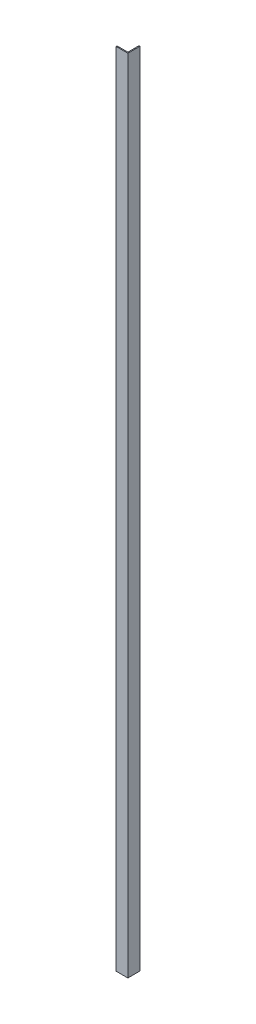
SolidWorks part; units mm, degrees
material "AISI 1035 Steel (SS)"
ref_plane "Front Plane" through (0, 0, 0) normal (0, 0, 1) x (1, 0, 0)
ref_plane "Top Plane" through (0, 0, 0) normal (0, 1, 0) x (1, 0, 0)
ref_plane "Right Plane" through (0, 0, 0) normal (1, 0, 0) x (0, 0, -1)
sketch "Sketch1" plane through (0, 0, 0) normal (0, 1, 0) x (1, 0, 0)
  line L0 (0, 0) -> (18, 0)
  line L1 (18, 0) -> (18, 18.4212)
  line L2 (0, 1.5) -> (16.5, 1.5)
  line L3 (16.5, 1.5) -> (16.5, 18.4212)
  line L4 (16.5, 18.4212) -> (18, 18.4212)
  line L5 (0, 1.5) -> (0, 0)
  dimension "D1" = 1.5
extrude "Boss-Extrude1" add sketch "Sketch1" along normal blind 1220
fillet "Fillet1" radius 1 1 edges at (16.5, 610, -1.5)
fillet "Fillet2" radius 1.2 1 edges at (16.5, 610, -18.4212) second distance 2 first distance on face at (17.25, 610, -18.4212)
fillet "Fillet3" radius 1.2 1 edges at (0, 610, -1.5) second distance 2 first distance on face at (0, 610, -0.75)
